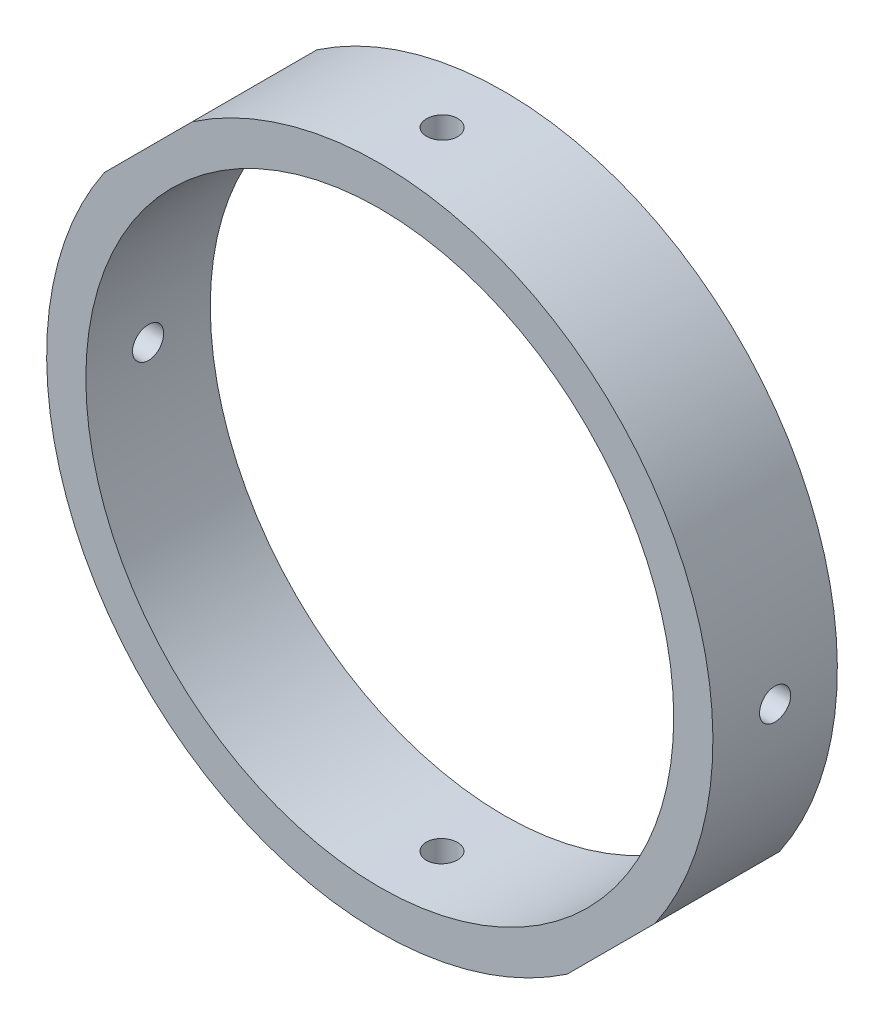
SolidWorks part; units mm, degrees
ref_plane "Alzado" through (0, 0, 0) normal (0, 0, 1) x (1, 0, 0)
ref_plane "Planta" through (0, 0, 0) normal (0, 1, 0) x (1, 0, 0)
ref_plane "Vista lateral" through (0, 0, 0) normal (1, 0, 0) x (0, 0, -1)
sketch "Croquis1" plane through (0, 0, 0) normal (0, 0, 1) x (1, 0, 0)
  line L0 (0, 0) -> (-24.0416, 24.0416) construction
  line L1 (0, 0) -> (21.2132, 21.2132) construction
  line L2 (0, 0) -> (0, 30) construction
  line L3 (-19.1285, 28.1087) -> (-28.1087, 19.1285)
  line L4 (28.1087, -19.1285) -> (19.1285, -28.1087)
  circle A0 centre (0, 0) radius 30
  arc A1 (-28.1087, 19.1285) -> (19.1285, -28.1087) centre (0, 0) ccw
  arc A2 (28.1087, -19.1285) -> (-19.1285, 28.1087) centre (0, 0) ccw
  point P10 (-23.6186, 23.6186)
  dimension "D1" = 60
  dimension "D2" = 4
  dimension "D3" = 45
  dimension "D4" = 12.7
extrude "Saliente-Extruir1" add sketch "Croquis1" along normal blind 6.35 and the other way blind 6.35
sketch "Croquis3" plane through (0, 0, 0) normal (0, 1, 0) x (1, 0, 0)
  circle A0 centre (0, 0) radius 1.5875
  dimension "D1" = 3.175
extrude "Cortar-Extruir1" cut sketch "Croquis3" against normal through all and the other way through all
sketch "Croquis4" plane through (0, 0, 0) normal (1, 0, 0) x (0, 0, -1)
  circle A0 centre (0, 0) radius 1.5875
  dimension "D1" = 3.175
extrude "Cortar-Extruir2" cut sketch "Croquis4" against normal through all and the other way through all
sketch "Croquis5" plane through (-23.6186, 23.6186, 0) normal (-0.7071, 0.7071, 0) x (0, 0, 1)
  line L0 (-6.35, 0) -> (6.35, 0) construction
  line L1 (-6.35, 6.35) -> (-6.35, -6.35) construction
  line L2 (6.35, 6.35) -> (6.35, -6.35) construction
  circle A0 centre (-3.5, 0) radius 1.75
  circle A1 centre (3.5, 0) radius 1.75
  dimension "D1" = 3.5
  dimension "D3" = 3.5
  dimension "D4" = 3.5
  dimension "D2" = 3.5
extrude "Cortar-Extruir3" cut sketch "Croquis5" against normal through all
